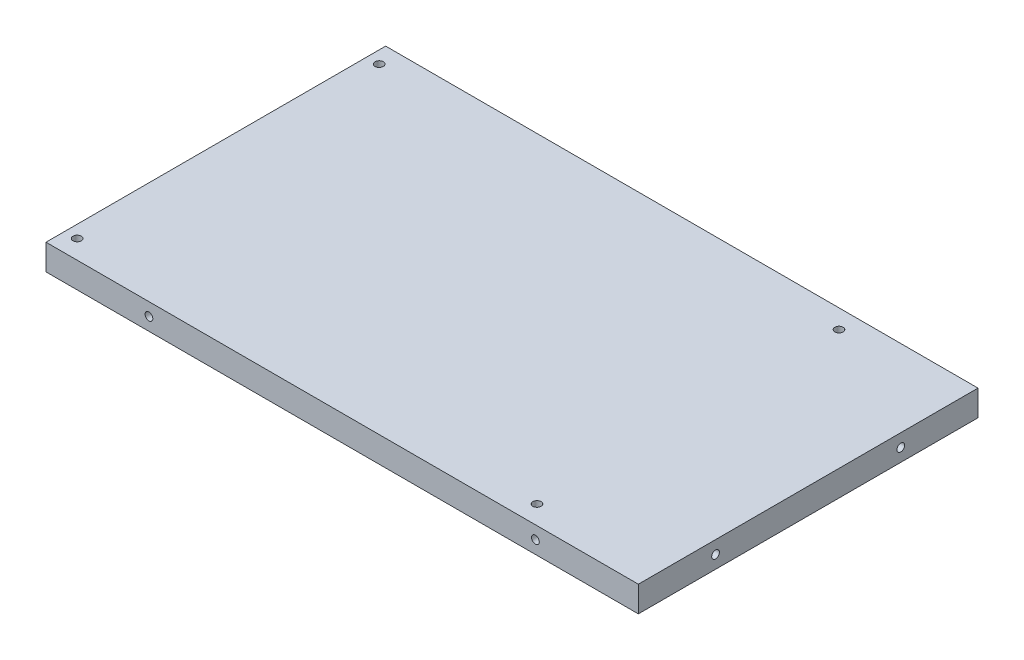
SolidWorks part; units mm, degrees
ref_plane "前视基准面" through (0, 0, 0) normal (0, 0, 1) x (1, 0, 0)
ref_plane "上视基准面" through (0, 0, 0) normal (0, 1, 0) x (1, 0, 0)
ref_plane "右视基准面" through (0, 0, 0) normal (1, 0, 0) x (0, 0, -1)
other "Configuration Table"
sketch "草图1" plane through (0, 0, 0) normal (0, 1, 0) x (1, 0, 0)
  line L1 (0, 0) -> (115.1, 0)
  line L2 (0, 0) -> (0, -66)
  line L3 (0, -66) -> (115.1, -66)
  line L4 (115.1, 0) -> (115.1, -66)
  line L9 (48.3, -13.5) -> (66.8, -13.5)
  line L10 (11.5, -18.7) -> (10.5, -18.7)
  line L11 (31.5, -33.5) -> (11.5, -33.5)
  line L12 (31.5, -33.5) -> (31.5, -13.5)
  line L13 (31.5, -13.5) -> (11.5, -13.5)
  line L14 (11.5, -33.5) -> (11.5, -13.5)
  line L15 (11.5, -18.7) -> (11.5, -20.2)
  line L16 (11.5, -20.2) -> (10.5, -20.2)
  line L17 (10.5, -18.7) -> (10.5, -20.2)
  line L22 (11.5, -29.6) -> (10.5, -29.6)
  line L23 (11.5, -29.6) -> (11.5, -31.1)
  line L24 (11.5, -31.1) -> (10.5, -31.1)
  line L25 (10.5, -29.6) -> (10.5, -31.1)
  line L26 (15, -33.5) -> (25, -33.5)
  line L27 (15, -33.5) -> (15, -39.7)
  line L28 (15, -39.7) -> (25, -39.7)
  line L29 (25, -33.5) -> (25, -39.7)
  line L30 (14, -33.5) -> (15, -33.5)
  line L31 (14, -33.5) -> (14, -34.5)
  line L32 (14, -34.5) -> (15, -34.5)
  line L33 (15, -33.5) -> (15, -34.5)
  line L34 (25, -34.5) -> (26, -34.5)
  line L35 (25, -34.5) -> (25, -33.5)
  line L36 (25, -33.5) -> (26, -33.5)
  line L37 (26, -34.5) -> (26, -33.5)
  line L38 (11.5, -13.5) -> (15, -13.5)
  line L39 (11.5, -13.5) -> (11.5, -16.5)
  line L40 (11.5, -16.5) -> (15, -16.5)
  line L41 (15, -13.5) -> (15, -16.5)
  line L42 (13.8, -15.3) -> (15, -15.3)
  line L43 (13.8, -15.3) -> (13.8, -16.5)
  line L44 (13.8, -16.5) -> (15, -16.5)
  line L45 (15, -15.3) -> (15, -16.5)
  line L46 (31.5, -13.5) -> (25, -13.5)
  line L47 (31.5, -13.5) -> (31.5, -19.9)
  line L48 (31.5, -19.9) -> (25, -19.9)
  line L49 (25, -13.5) -> (25, -19.9)
  line L50 (25, -19.9) -> (28.4, -19.9)
  line L51 (25, -19.9) -> (25, -16.5)
  line L52 (25, -16.5) -> (28.4, -16.5)
  line L53 (28.4, -19.9) -> (28.4, -16.5)
  line L54 (25, -16.5) -> (26.2, -16.5)
  line L55 (25, -16.5) -> (25, -15.3)
  line L56 (25, -15.3) -> (26.2, -15.3)
  line L57 (26.2, -16.5) -> (26.2, -15.3)
  line L58 (28.4, -19.9) -> (29.6, -19.9)
  line L59 (28.4, -19.9) -> (28.4, -18.7)
  line L60 (28.4, -18.7) -> (29.6, -18.7)
  line L61 (29.6, -19.9) -> (29.6, -18.7)
  line L62 (31.5, -33.5) -> (28.3, -33.5)
  line L63 (31.5, -33.5) -> (31.5, -29.9)
  line L64 (31.5, -29.9) -> (28.3, -29.9)
  line L65 (28.3, -33.5) -> (28.3, -29.9)
  line L66 (28.3, -29.9) -> (29.5, -29.9)
  line L67 (28.3, -29.9) -> (28.3, -31.1)
  line L68 (28.3, -31.1) -> (29.5, -31.1)
  line L69 (29.5, -29.9) -> (29.5, -31.1)
  line L70 (48.3, -13.5) -> (48.3, -16.5)
  line L71 (48.3, -16.5) -> (66.8, -16.5)
  line L72 (66.8, -13.5) -> (66.8, -16.5)
  circle A2 centre (45.78, -15) radius 0.75
  circle A3 centre (69.32, -15) radius 0.75
  circle A4 centre (45.78, -38.545) radius 0.75
  circle A5 centre (69.32, -38.545) radius 0.75
  point P11 (57.55, -13.5)
  point P12 (57.55, 0)
  dimension "D28" = 1.5
  dimension "D29" = 66
  dimension "D1" = 115.1
  dimension "D3" = 3
  dimension "D4" = 13.5
  dimension "D5" = 11.5
  dimension "D6" = 31.5
  dimension "D7" = 20
  dimension "D8" = 1
  dimension "D9" = 1.5
  dimension "D10" = 5.2
  dimension "D11" = 9.4
  dimension "D12" = 6.2
  dimension "D13" = 3.5
  dimension "D14" = 10
  dimension "D15" = 1
  dimension "D16" = 3
  dimension "D17" = 3.5
  dimension "D18" = 1.2
  dimension "D19" = 6.5
  dimension "D20" = 6.4
  dimension "D21" = 3.4
  dimension "D22" = 3.4
  dimension "D23" = 1.2
  dimension "D24" = 3.6
  dimension "D25" = 3.2
  dimension "D26" = 1.2
  dimension "D27" = 18.5
extrude "凸台-拉伸1" add sketch "草图1" along normal blind 5 contours L2 L3 L4 L1
sketch "草图2" plane through (0, 5, 0) normal (0, 1, 0) x (1, 0, 0)
  circle A0 centre (2.4, -62.35) radius 0.8
  circle A1 centre (2.4, -3.6565) radius 0.8
  circle A2 centre (91.75, -62.35) radius 0.8
  circle A3 centre (91.75, -3.6565) radius 0.8
  dimension "D1" = 1.6
  dimension "D2" = 89.35
extrude "切除-拉伸1" cut sketch "草图2" against normal blind 3 contours A2 | A3 | A0 | A1
sketch "草图3" plane through (0, 0, 0) normal (-1, 0, 0) x (0, 0, 1)
  line L0 (0, 5) -> (66, 5) construction
  line L1 (0, 5) -> (0, 0) construction
  line L2 (66, 5) -> (66, 0) construction
  circle A0 centre (51, 2.5) radius 0.75
  circle A1 centre (15, 2.5) radius 0.75
  dimension "D1" = 1.5
  dimension "D2" = 2.5
  dimension "D3" = 15
  dimension "D4" = 15
extrude "切除-拉伸2" cut sketch "草图3" against normal blind 4 contours A1 | A0
extrude "切除-拉伸3" cut sketch "草图3<3>" along normal blind 4 from surface starting at face at (115.1, 2.5, 33)
sketch "草图3<3>" plane through (0, 0, 0) normal (-1, 0, 0) x (0, 0, 1) same geometry as "草图3"
sketch "草图4" plane through (0, 0, 66) normal (0, 0, 1) x (1, 0, 0)
  line L0 (0, 5) -> (115.1, 5) construction
  line L1 (0, 5) -> (0, 0) construction
  line L2 (115.1, 5) -> (115.1, 0) construction
  circle A0 centre (20, 2.5) radius 0.75
  circle A1 centre (95.1, 2.5) radius 0.75
  dimension "D1" = 1.5
  dimension "D2" = 2.5
  dimension "D3" = 20
  dimension "D4" = 20
extrude "切除-拉伸4" cut sketch "草图4" against normal blind 4
extrude "切除-拉伸5" cut sketch "草图4<2>" along normal blind 4 from surface starting at face at (57.55, 2.5, 0)
sketch "草图4<2>" plane through (0, 0, 66) normal (0, 0, 1) x (1, 0, 0) same geometry as "草图4"
sketch "草图5" plane through (0, 0, 0) normal (0, -1, 0) x (1, 0, 0)
  circle A0 centre (72.6, 8.8) radius 0.75
  circle A1 centre (42.5, 8.8) radius 0.75
  circle A2 centre (72.6, 57.2) radius 0.75
  circle A3 centre (42.5, 57.2) radius 0.75
  dimension "D1" = 1.5
extrude "切除-拉伸6" cut sketch "草图5" against normal blind 3 contours A2 | A3 | A1 | A0
